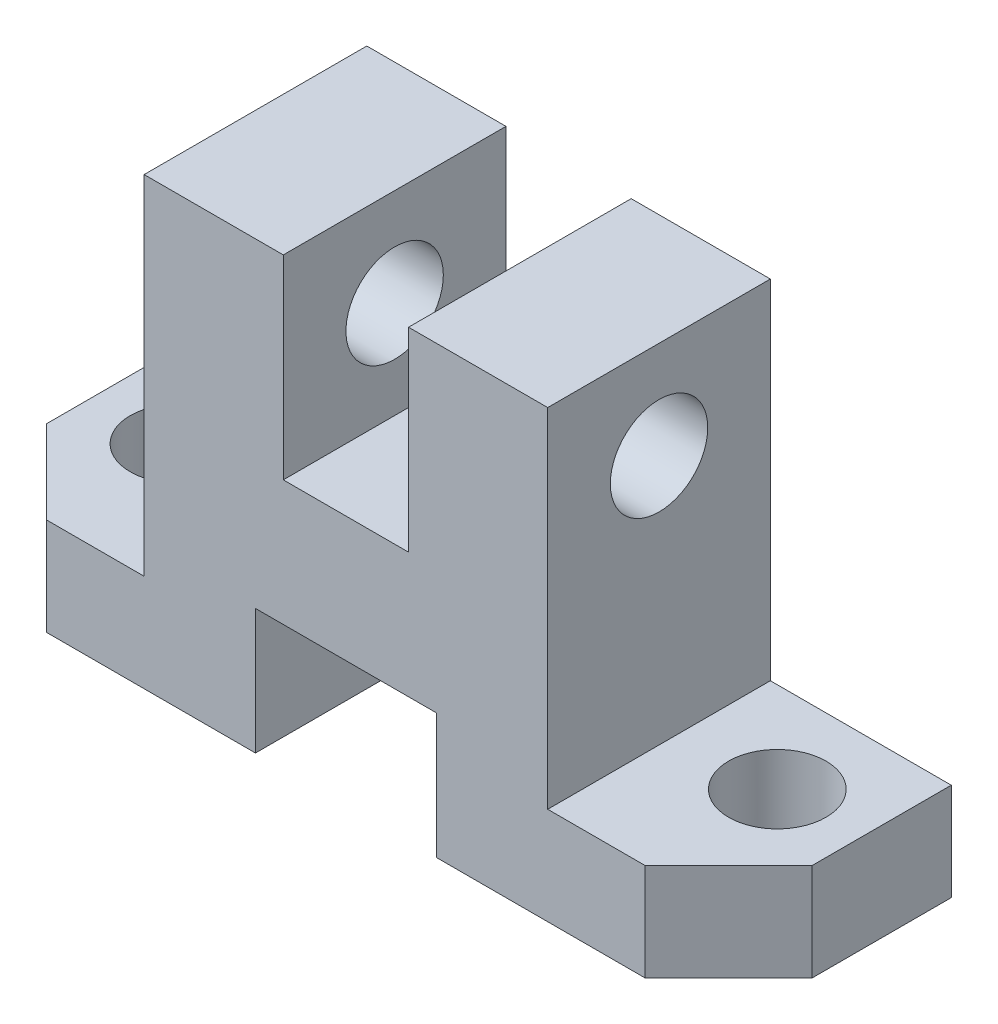
SolidWorks part; units mm, degrees
ref_plane "Front Plane" through (0, 0, 0) normal (0, 0, 1) x (1, 0, 0)
ref_plane "Top Plane" through (0, 0, 0) normal (0, 1, 0) x (1, 0, 0)
ref_plane "Right Plane" through (0, 0, 0) normal (1, 0, 0) x (0, 0, -1)
sketch "Sketch1" plane through (0, 0, 0) normal (0, 0, 1) x (1, 0, 0)
  line L0 (4.5, 0) -> (-4.5, 0)
  line L1 (-4.5, 0) -> (-4.5, 14)
  line L2 (-4.5, 14) -> (-14.5, 14)
  line L3 (-14.5, 14) -> (-14.5, -11)
  line L4 (-14.5, -11) -> (-27.5, -11)
  line L5 (-27.5, -11) -> (-27.5, -18)
  line L6 (-27.5, -18) -> (-6.5, -18)
  line L7 (-6.5, -18) -> (-6.5, -9)
  line L8 (-6.5, -9) -> (6.5, -9)
  line L10 (6.5, -18) -> (6.5, -9)
  line L11 (27.5, -18) -> (6.5, -18)
  line L12 (27.5, -11) -> (27.5, -18)
  line L13 (14.5, -11) -> (27.5, -11)
  line L14 (14.5, 14) -> (14.5, -11)
  line L15 (4.5, 14) -> (14.5, 14)
  line L16 (4.5, 0) -> (4.5, 14)
  point P0 (0, 0)
  point P11 (0, 0)
  point P21 (0, -9)
  dimension "D1" = 13
  dimension "D2" = 9
  dimension "D3" = 7
  dimension "D4" = 13
  dimension "D5" = 10
  dimension "D6" = 6.5
  dimension "D7" = 32
  dimension "D8" = 14
  dimension "D9" = 9
extrude "Boss-Extrude1" add sketch "Sketch1" against normal blind 16 contours L2 L3 L4 L5 L6 L7 L8 L10 L11 L12 L13 L14 L15 L16 L0 L1
sketch "Sketch2" plane through (14.5, 0, 0) normal (1, 0, 0) x (0, 0, -1)
  line L0 (16, 14) -> (16, -11) construction
  line L1 (16, 14) -> (0, 14) construction
  circle A0 centre (8, 7) radius 3.5
  point P4 (0, 0)
  point P6 (22.7145, 13.8416)
  dimension "D1" = 7
  dimension "D2" = 8
  dimension "D3" = 7
extrude "Cut-Extrude1" cut sketch "Sketch2" against normal through all both and the other way through all
chamfer "Chamfer1" distance 6 angle 45 1 edges at (-27.5, -14.5, 0)
chamfer "Chamfer2" distance 6 angle 45 1 edges at (27.5, -14.5, 0)
sketch "Sketch6" plane through (0, -11, 0) normal (0, 1, 0) x (1, 0, 0)
  line L0 (-14.5, 16) -> (-27.5, 16) construction
  circle A0 centre (-21.5, 9.5) radius 3.5
  circle A1 centre (21.5, 9.5) radius 3.5
  point P4 (-21, 16)
  point P9 (0, 0)
  dimension "D1" = 7
  dimension "D2" = 6.5
extrude "Cut-Extrude2" cut sketch "Sketch6" against normal blind 16 and the other way through all contours A0
extrude "Cut-Extrude3" cut sketch "Sketch6<3>" against normal blind 16 contours A1
sketch "Sketch6<3>" plane through (0, -11, 0) normal (0, 1, 0) x (1, 0, 0) same geometry as "Sketch6"
